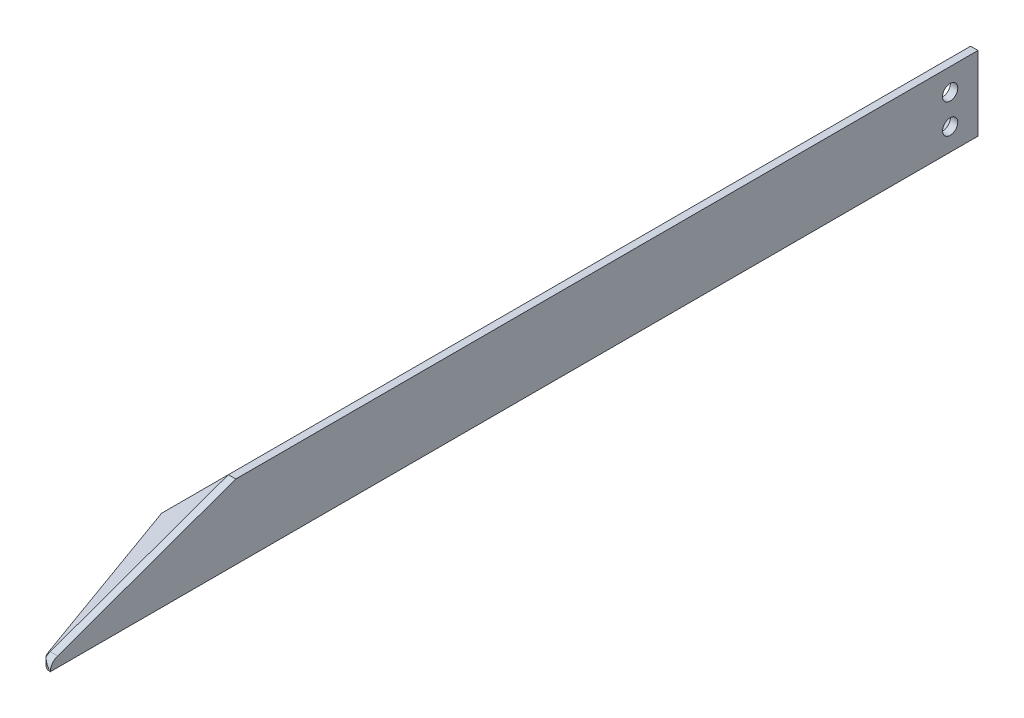
SolidWorks part; units mm, degrees
ref_plane "前视基准面" through (0, 0, 0) normal (0, 0, 1) x (1, 0, 0)
ref_plane "上视基准面" through (0, 0, 0) normal (0, 1, 0) x (1, 0, 0)
ref_plane "右视基准面" through (0, 0, 0) normal (1, 0, 0) x (0, 0, -1)
sketch "草图1" plane through (0, 0, 0) normal (0, 0, 1) x (1, 0, 0)
  line L0 (-20, 0) -> (0, 0)
  line L1 (0, 0) -> (0, 20)
  line L2 (-20, 0) -> (-20, 2)
  line L3 (-20, 2) -> (-2, 2)
  line L4 (-2, 2) -> (-2, 20)
  line L5 (-2, 20) -> (0, 20)
  dimension "D1" = 20
  dimension "D2" = 20
  dimension "D3" = 2
extrude "凸台-拉伸1" add sketch "草图1" along normal blind 250
sketch "草图2" plane through (-2, 0, 0) normal (-1, 0, 0) x (0, 0, 1)
  line L0 (250, 2) -> (200, 20)
  line L1 (250, 20) -> (0, 20) construction
  line L2 (200, 20) -> (250, 20)
  line L3 (250, 20) -> (250, 2)
  dimension "D1" = 50
extrude "切除-拉伸1" cut sketch "草图2" against normal blind 10
sketch "草图3" plane through (0, 2, 0) normal (0, 1, 0) x (1, 0, 0)
  line L0 (-2, -250) -> (-20, -200)
  line L1 (-20, -250) -> (-20, 0) construction
  line L2 (-20, -200) -> (-20, -250)
  line L3 (-20, -250) -> (-2, -250)
extrude "切除-拉伸2" cut sketch "草图3" against normal blind 10
fillet "圆角1" radius 3 2 edges at (-1, 2, 250) (-2, 1, 250)
sketch "草图4" plane through (0, 0, 0) normal (1, 0, 0) x (0, 0, -1)
  line L0 (-250, 0) -> (0, 0) construction
  line L1 (0, 0) -> (0, 20) construction
  line L2 (-200, 20) -> (0, 20) construction
  circle A0 centre (-7.5, 6) radius 2.05
  circle A1 centre (-7.5, 14) radius 2.05
  dimension "D1" = 4.1
  dimension "D4" = 6
  dimension "D2" = 6
  dimension "D3" = 7.5
extrude "切除-拉伸3" cut sketch "草图4" against normal blind 10
